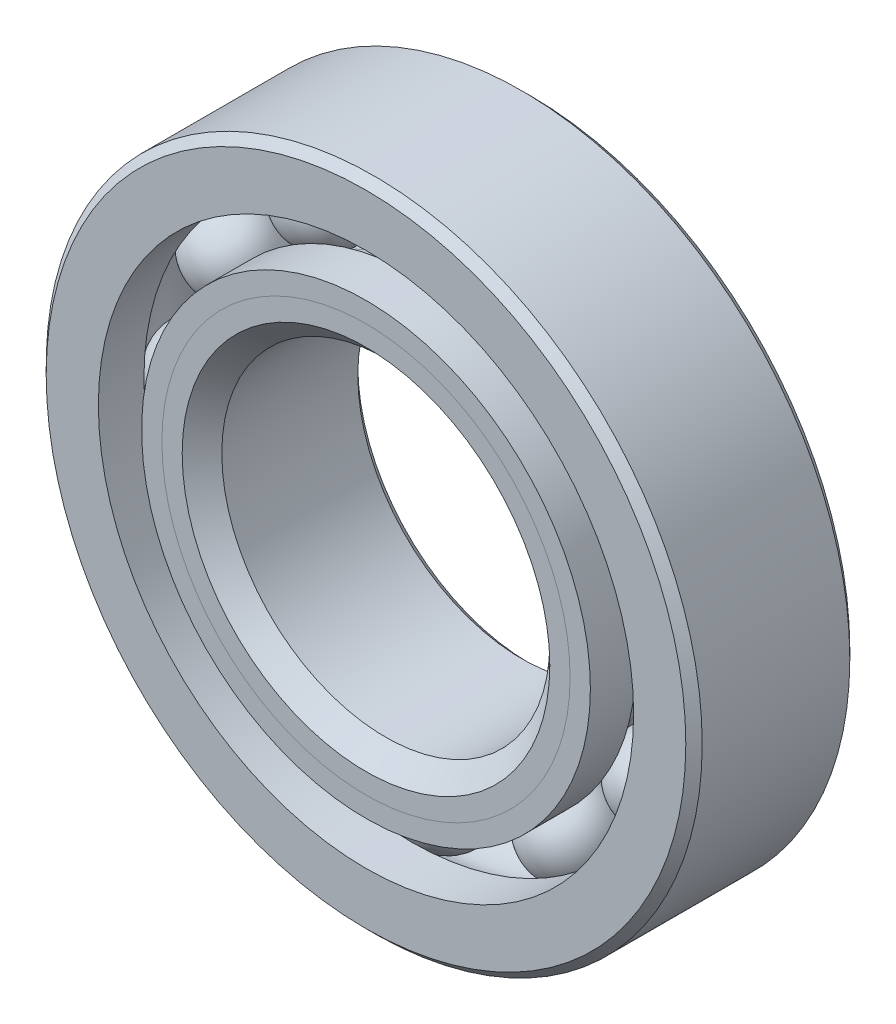
SolidWorks part; units mm, degrees
ref_plane "Front Plane" through (0, 0, 0) normal (0, 0, 1) x (1, 0, 0)
ref_plane "Top Plane" through (0, 0, 0) normal (0, 1, 0) x (1, 0, 0)
ref_plane "Right Plane" through (0, 0, 0) normal (1, 0, 0) x (0, 0, -1)
sketch "Sketch1" plane through (0, 0, 0) normal (1, 0, 0) x (0, 0, -1)
  line L0 (-7.9375, 0) -> (7.9375, 0) construction
  line L1 (0, 31.75) -> (0, -31.75) construction
  line L2 (7.1437, 31.75) -> (-7.1438, 31.75)
  line L3 (-7.1438, 31.75) -> (-7.9375, 30.9563)
  line L4 (-7.9375, 30.9563) -> (-7.9375, 25.9059)
  line L5 (-7.9375, 25.9059) -> (-3.5278, 25.9059)
  line L6 (7.9375, 25.9059) -> (3.5278, 25.9059)
  line L7 (7.9375, 30.9563) -> (7.9375, 25.9059)
  line L8 (7.1437, 31.75) -> (7.9375, 30.9563)
  line L9 (0, 31.75) -> (0, 23.8125) construction
  line L10 (0, 23.8125) -> (0, 15.875) construction
  arc A0 (-3.5278, 25.9059) -> (3.5278, 25.9059) centre (0, 23.8125) cw
  point P14 (0, 15.875)
  dimension "D3" = 7.0556
  dimension "D1" = 45
  dimension "Width" = 15.875
  dimension "OD" = 63.5
  dimension "D2" = 0.7937
  dimension "Shaft Dia" = 31.75
  dimension "D4" = 2.0934
revolve "Revolve1" add sketch "Sketch1" angle 360 about L0
sketch "Sketch2" plane through (0, 0, 0) normal (1, 0, 0) x (0, 0, -1)
  line L0 (-7.9375, 21.7191) -> (-3.5278, 21.7191)
  line L1 (-7.9375, 30.9563) -> (-7.9375, -30.9563) construction
  line L2 (-7.9375, 21.7191) -> (-7.9375, 19.7559)
  line L3 (-7.9375, 19.7559) -> (-5.9743, 17.7927)
  line L4 (-5.9743, 17.7927) -> (0, 17.7927)
  line L5 (0, 31.75) -> (0, -31.75) construction
  line L6 (0, 17.7927) -> (0, 19.7104)
  line L7 (0, 19.7104) -> (0, 15.875) construction
  line L8 (-7.9375, 21.7191) -> (-7.9375, 17.7927) construction
  line L9 (-7.9375, 17.7927) -> (-5.9743, 17.7927) construction
  arc A0 (-3.5278, 21.7191) -> (0, 19.7104) centre (0, 23.8125) ccw
  arc A1 (3.5278, 25.9059) -> (-3.5278, 25.9059) centre (0, 23.8125) ccw construction
  circle A2 centre (0, 23.8125) radius 4.1021 construction
  dimension "D1" = 45
revolve "Revolve2" add sketch "Sketch2" angle 360 about L0
sketch "Sketch3" plane through (0, 0, 0) normal (1, 0, 0) x (0, 0, -1)
  line L0 (-7.9375, 19.7559) -> (-5.9743, 17.7927)
  line L1 (-5.9743, 17.7927) -> (0, 17.7927)
  line L2 (0, 17.7927) -> (0, 19.7104)
  line L3 (-7.9375, 19.7559) -> (-7.9375, 17.7927)
  line L4 (-7.9375, 21.7191) -> (-7.9375, 17.7927) construction
  line L5 (-7.9375, 17.7927) -> (-6.0198, 15.875)
  line L6 (-6.0198, 15.875) -> (7.1438, 15.875)
  line L7 (7.1438, 31.75) -> (7.1438, -31.75) construction
  line L8 (7.1438, 15.875) -> (7.9375, 16.6687)
  line L9 (7.9375, -30.9563) -> (7.9375, 30.9563) construction
  line L10 (7.9375, 16.6687) -> (7.9375, 21.7191)
  line L11 (7.9375, 21.7191) -> (3.5278, 21.7191)
  line L13 (7.1437, 31.75) -> (7.9375, 30.9563) construction
  circle A0 centre (0, 23.8125) radius 4.1021 construction
  arc A1 (3.5278, 21.7191) -> (0, 19.7104) centre (0, 23.8125) cw
revolve "Revolve3" add sketch "Sketch3" angle 360 about L0
sketch "Sketch4" plane through (0, 0, 0) normal (1, 0, 0) x (0, 0, -1)
  line L0 (-4.1021, 23.8125) -> (4.1021, 23.8125)
  circle A1 centre (0, 23.8125) radius 4.1021 construction
  arc A2 (-4.1021, 23.8125) -> (4.1021, 23.8125) centre (0, 23.8125) cw
  arc A3 (3.5278, 25.9059) -> (-3.5278, 25.9059) centre (0, 23.8125) ccw construction
revolve "Revolve4" add sketch "Sketch4" angle 360 about L0
ref_axis "Axis1" through (0, 0, -7.9375) along (0, 0, 1)
pattern_circular "CirPattern1" count 12 every 30 about axis through (0, 0, -7.9375) along (0, 0, 1) of bodies 104
equation "\"D2@Sketch1\" = \"Width@Sketch1\"*.05"
equation "\"D3@Sketch1\" = \"Width@Sketch1\"/2.25"
equation "\"D4@Sketch1\" = (((\"OD@Sketch1\"-\"Width@Sketch1\")/2)/3.25)/3.5"
equation "\"D2@CirPattern1\" = 360/\"Balls@CirPattern1\""
